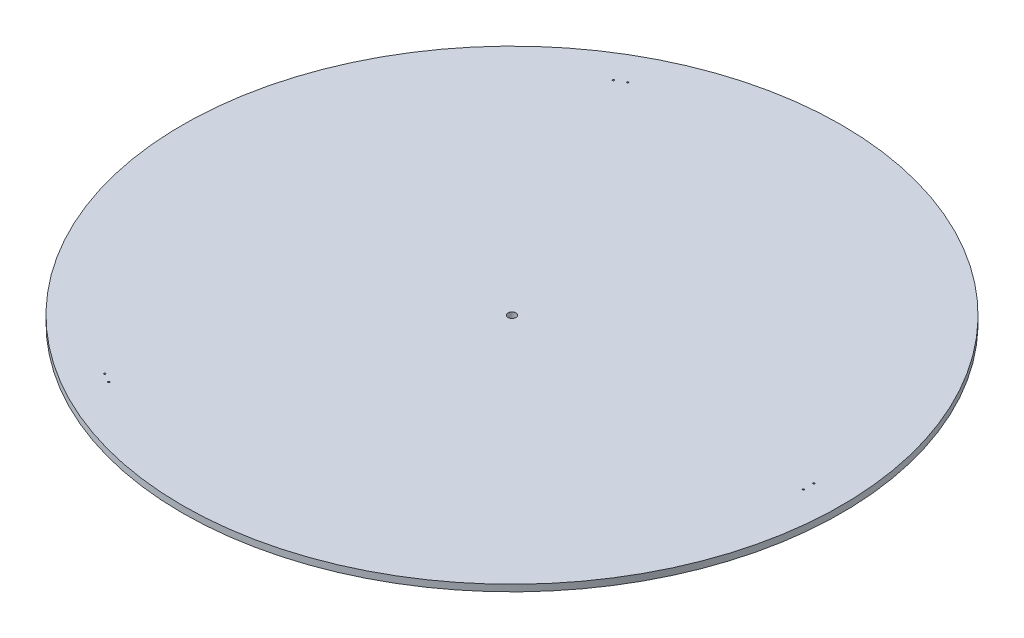
SolidWorks part; units mm, degrees
ref_plane "Plan de face" through (0, 0, 0) normal (0, 0, 1) x (1, 0, 0)
ref_plane "Plan de dessus" through (0, 0, 0) normal (0, 1, 0) x (1, 0, 0)
ref_plane "Plan de droite" through (0, 0, 0) normal (1, 0, 0) x (0, 0, -1)
sketch "Esquisse1" plane through (0, 0, 0) normal (0, 1, 0) x (1, 0, 0)
  circle A0 centre (0, 0) radius 500
  dimension "D1" = 1000
extrude "Boss.-Extru.1" add sketch "Esquisse1" along normal mid plane 10
sketch "Esquisse5" plane through (0, 5, 0) normal (0, 1, 0) x (1, 0, 0)
  point P0 (0, 0)
hole_wizard "Dégagement M101" positions "Esquisse5" profile "Esquisse4" hole size "M10" standard "ISO" end condition through all
sketch "Esquisse4" plane through (0, 5, 0) normal (1, 0, 0) x (0, 0, 1)
  line L0 (0, 0) -> (0, 10)
  line L1 (0, 10) -> (6, 10)
  line L2 (6, 10) -> (6, 0.025)
  line L3 (6, 0.025) -> (6.025, 0)
  line L5 (6.025, 0) -> (0, 0)
  line L6 (-6, 0.025) -> (-6.025, 0) construction
  line L11 (0, -6.35) -> (0, 107.95) construction
  dimension "Diamètre du perçage jusqu'au prochain" = 12
  dimension "Profondeur du perçage jusqu'au prochain" = 10
  dimension "Diamètre du fraisage entrant" = 12.05
  dimension "Angle du fraisage entrant" = 90
sketch "Esquisse6" plane through (0, 5, 0) normal (0, 1, 0) x (1, 0, 0)
  line L0 (0, 0) -> (458.2969, 0) construction
  line L1 (0, 0) -> (-167.1022, 289.4294) construction
  line L2 (0, 0) -> (-171.7601, -297.4973) construction
  circle A0 centre (450, 8) radius 1.25
  circle A5 centre (450, -8) radius 1.25
  point P13 (458.2969, 0)
  point P15 (0, 0)
  dimension "D5" = 2.5
  dimension "D3" = 8
  dimension "D4" = 450
  dimension "D1" = 120
  dimension "D2" = 120
extrude "Enlèv. mat.-Extru.1" cut sketch "Esquisse6" against normal through all
pattern_circular "Répétition circulaire1" count 3 over 360 about axis through (0, 5, 0) along (0, 1, 0) of "Enlèv. mat.-Extru.1" reverse direction yes
